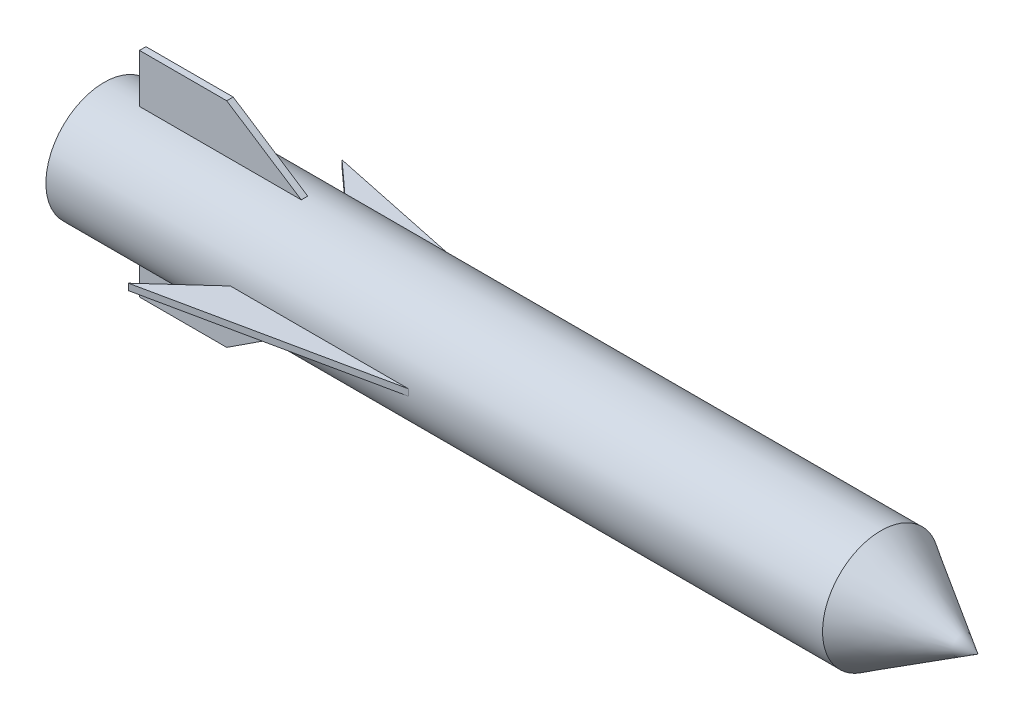
SolidWorks part; units mm, degrees
ref_plane "Front Plane" through (0, 0, 0) normal (0, 0, 1) x (1, 0, 0)
ref_plane "Top Plane" through (0, 0, 0) normal (0, 1, 0) x (1, 0, 0)
ref_plane "Right Plane" through (0, 0, 0) normal (1, 0, 0) x (0, 0, -1)
sketch "Sketch1" plane through (0, 0, 0) normal (1, 0, 0) x (0, 0, -1)
  circle A0 centre (0, 0) radius 4572
  dimension "D1" = 9144
extrude "Boss-Extrude1" add sketch "Sketch1" along normal blind 30480 and the other way blind 30480
sketch "Sketch3" plane through (0, 0, 0) normal (0, 1, 0) x (1, 0, 0)
  line L0 (30480, 0) -> (38100, 0)
  line L1 (30480, -4572) -> (30480, 4572) construction
  line L2 (38100, 0) -> (30480, 4579.0501)
  line L3 (30480, 4579.0501) -> (30480, 0)
  dimension "D1" = 7620
  dimension "D2" = 8890
revolve "Revolve1" add sketch "Sketch3" angle 360 about L0
sketch "Sketch4" plane through (0, 0, 0) normal (0, 0, 1) x (1, 0, 0)
  line L0 (-27453.9198, 4572) -> (-27453.9198, 8382)
  line L1 (30480, 4572) -> (-30480, 4572) construction
  line L2 (-27453.9198, 8382) -> (-20608.3306, 8382)
  line L3 (-20608.3306, 8382) -> (-14753.9198, 4572)
  line L4 (-14753.9198, 4572) -> (-27453.9198, 4572)
  line L10 (-27453.9198, -4572) -> (-27453.9198, -8382)
  line L11 (-30480, -4572) -> (30480, -4572) construction
  line L12 (-27453.9198, -8382) -> (-20608.3306, -8382)
  line L13 (-20608.3306, -8382) -> (-14753.9198, -4572)
  line L14 (-14753.9198, -4572) -> (-27453.9198, -4572)
  point P11 (0, 0)
  point P13 (0, 0)
  dimension "D1" = 3810
  dimension "D2" = 6985
  dimension "D3" = 12700
extrude "Boss-Extrude2" add sketch "Sketch4" along normal blind 254 and the other way blind 254 separate body
sketch "Sketch5" plane through (0, 0, 0) normal (0, 1, 0) x (1, 0, 0)
  line L0 (-2032, 4572) -> (-20193, 8382)
  line L1 (30480, 4572) -> (-30480, 4572) construction
  line L2 (-20193, 8382) -> (-16002, 4572)
  line L3 (-16002, 4572) -> (-2032, 4572)
  line L4 (-30480, 4572) -> (-30480, -4572) construction
  line L5 (-2032, -4572) -> (-20193, -8382)
  line L6 (-30480, -4572) -> (30480, -4572) construction
  line L7 (-20193, -8382) -> (-16002, -4572)
  line L8 (-16002, -4572) -> (-2032, -4572)
  point P11 (0, 0)
  point P13 (0, 0)
  point P14 (-19495.8852, -9029.9533)
  dimension "D1" = 18161
  dimension "D2" = 3810
  dimension "D3" = 28448
  dimension "D4" = 14478
extrude "Boss-Extrude3" add sketch "Sketch5" along normal blind 254 and the other way blind 254 separate body
